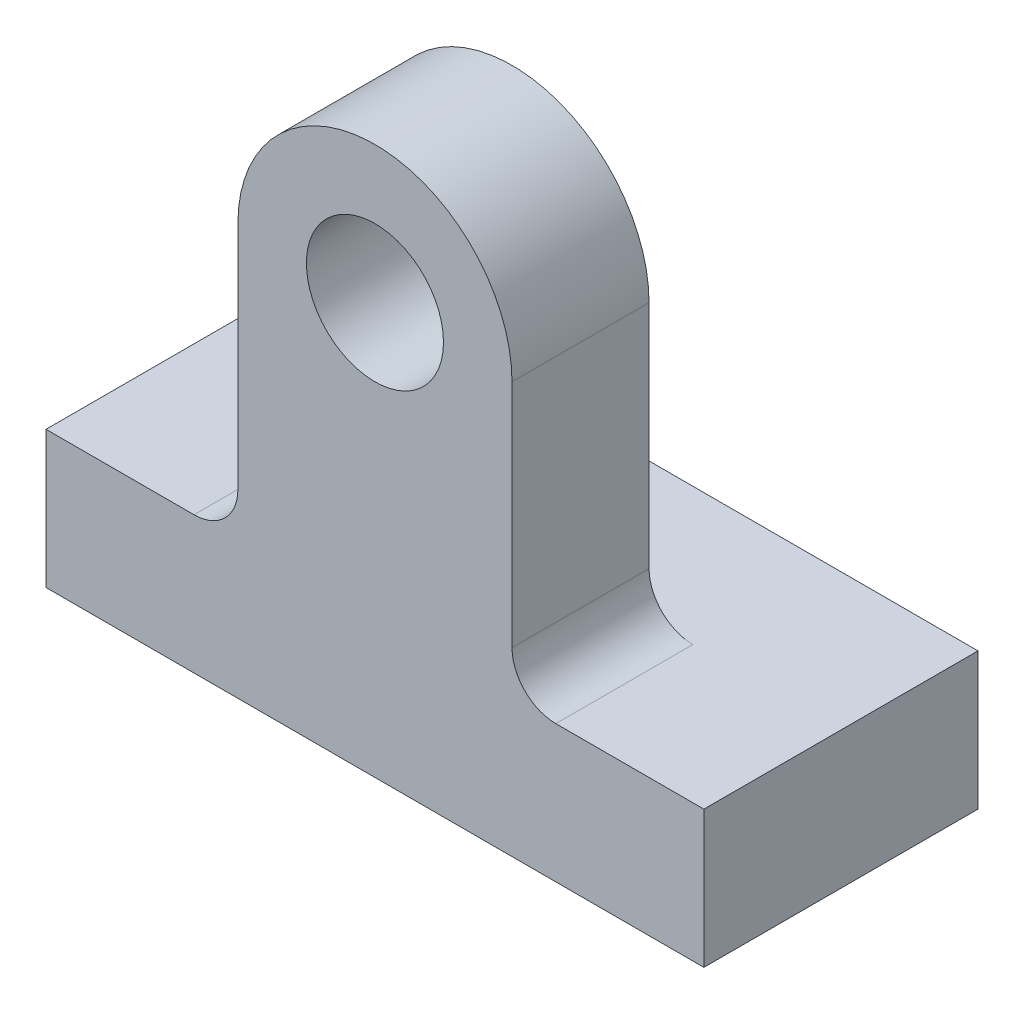
SolidWorks part; units mm, degrees
ref_plane "Front Plane" through (0, 0, 0) normal (0, 0, 1) x (1, 0, 0)
ref_plane "Top Plane" through (0, 0, 0) normal (0, 1, 0) x (1, 0, 0)
ref_plane "Right Plane" through (0, 0, 0) normal (1, 0, 0) x (0, 0, -1)
sketch "Rectangle Sketch" plane through (0, 0, 0) normal (0, 1, 0) x (1, 0, 0)
  line L1 (0, 0) -> (3048, 0)
  line L2 (0, 0) -> (0, -1270)
  line L3 (0, -1270) -> (3048, -1270)
  line L4 (3048, 0) -> (3048, -1270)
  dimension "D1" = 1270
  dimension "D2" = 3048
extrude "RectangleExtrude" add sketch "Rectangle Sketch" along normal blind 635
sketch "CurvedRectangleSketch" plane through (0, 0, 1270) normal (0, 0, 1) x (1, 0, 0)
  line L0 (889, 635) -> (889, 1905)
  line L1 (0, 635) -> (3048, 635) construction
  line L2 (2159, 635) -> (2159, 1905)
  line L3 (889, 635) -> (2159, 635)
  arc A0 (889, 1905) -> (2159, 1905) centre (1524, 1905) cw
  circle A1 centre (1524, 1905) radius 317.5
  dimension "D1" = 635
  dimension "D3" = 1270
  dimension "D2" = 889
extrude "CurvedRectangleExtrude" add sketch "CurvedRectangleSketch" against normal blind 635 contours A0 L2 L3 L0 | A1
fillet "CurvedRectangleFillet" radius 203.2 2 edges at (2159, 635, 952.5) (889, 635, 952.5)
sketch "Sketch1" plane through (0, 0, 635) normal (0, 0, -1) x (-1, 0, 0)
  line L0 (-2204.1701, 1115.2694) -> (-2852.1046, 1863.1341)
